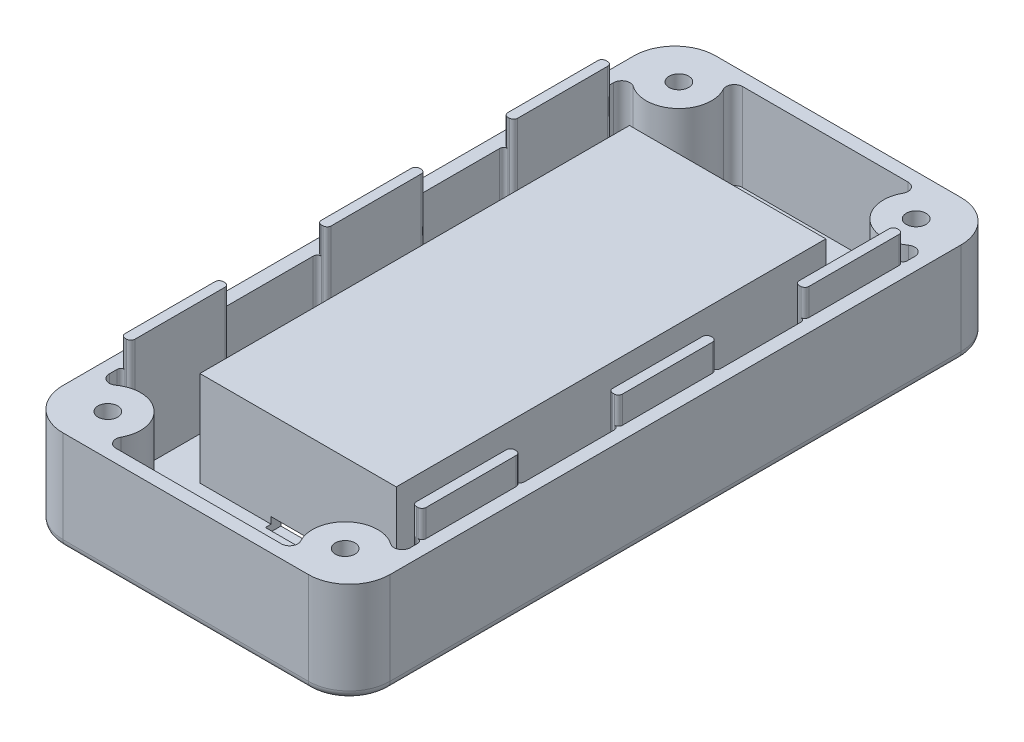
SolidWorks part; units mm, degrees
ref_plane "Front Plane" through (0, 0, 0) normal (0, 0, 1) x (1, 0, 0)
ref_plane "Top Plane" through (0, 0, 0) normal (0, 1, 0) x (1, 0, 0)
ref_plane "Right Plane" through (0, 0, 0) normal (1, 0, 0) x (0, 0, -1)
sketch "Base Sketch" plane through (0, 0, 0) normal (0, 1, 0) x (1, 0, 0)
  line L1 (0, 0) -> (40, 0)
  line L2 (0, 0) -> (0, 79.79)
  line L3 (0, 79.79) -> (40, 79.79)
  line L4 (40, 0) -> (40, 79.79)
extrude "Base" add sketch "Base Sketch" along normal blind 12.3
fillet "Corner Rounds R5" radius 5 4 edges at (0, 6.15, -79.79) (40, 6.15, -79.79) (40, 6.15, 0) (0, 6.15, 0)
shell "Shell" thickness 1.6 removed face at (20, 12.3, -39.895)
sketch "Sketch2" plane through (0, 0, 0) normal (0, 1, 0) x (1, 0, 0)
  circle A0 centre (5.5, 5) radius 4
  circle A1 centre (34.5, 5) radius 4
  circle A2 centre (5.5, 74.79) radius 4
  circle A3 centre (34.5, 74.79) radius 4
extrude "Screw Bosses" add sketch "Sketch2" along normal blind 12.3
sketch "Sketch3" plane through (0, 0, 0) normal (0, 1, 0) x (1, 0, 0)
  line L1 (1.6, 10.5) -> (2.8, 10.5)
  line L2 (1.6, 10.5) -> (1.6, 22.5)
  line L3 (1.6, 22.5) -> (2.8, 22.5)
  line L4 (2.8, 10.5) -> (2.8, 22.5)
  line L6 (1.6, 34.5) -> (2.8, 34.5)
  line L7 (1.6, 34.5) -> (1.6, 46.5)
  line L8 (1.6, 46.5) -> (2.8, 46.5)
  line L9 (2.8, 34.5) -> (2.8, 46.5)
  line L11 (1.6, 57.29) -> (2.8, 57.29)
  line L12 (1.6, 57.29) -> (1.6, 69.29)
  line L13 (1.6, 69.29) -> (2.8, 69.29)
  line L14 (2.8, 57.29) -> (2.8, 69.29)
  line L16 (37.2, 10.5) -> (38.4, 10.5)
  line L17 (37.2, 10.5) -> (37.2, 22.5)
  line L18 (37.2, 22.5) -> (38.4, 22.5)
  line L19 (38.4, 10.5) -> (38.4, 22.5)
  line L21 (37.2, 34.5) -> (38.4, 34.5)
  line L22 (37.2, 34.5) -> (37.2, 46.5)
  line L23 (37.2, 46.5) -> (38.4, 46.5)
  line L24 (38.4, 34.5) -> (38.4, 46.5)
  line L26 (37.2, 57.29) -> (38.4, 57.29)
  line L27 (37.2, 57.29) -> (37.2, 69.29)
  line L28 (37.2, 69.29) -> (38.4, 69.29)
  line L29 (38.4, 57.29) -> (38.4, 69.29)
extrude "Alignment Tabs" add sketch "Sketch3" along normal blind 15.6
fillet "Bottom Edge Round R1" radius 1 8 edges at (1.4645, 0, -1.4645) (20, 0, 0) (38.5355, 0, -1.4645) (40, 0, -39.895) (38.5355, 0, -78.3255) (20, 0, -79.79) (1.4645, 0, -78.3255) (0, 0, -39.895)
sketch "Sketch4" plane through (0, 0, 0) normal (0, 1, 0) x (1, 0, 0)
  circle A0 centre (5.5, 5) radius 1.2
  circle A1 centre (34.5, 5) radius 1.2
  circle A2 centre (5.5, 74.79) radius 1.2
  circle A3 centre (34.5, 74.79) radius 1.2
extrude "M2 Clearance Holes" cut sketch "Sketch4" along normal through all
sketch "Sketch5" plane through (0, 0, 0) normal (0, 1, 0) x (1, 0, 0)
  circle A0 centre (5.5, 5) radius 2.2
  circle A1 centre (34.5, 5) radius 2.2
  circle A2 centre (5.5, 74.79) radius 2.2
  circle A3 centre (34.5, 74.79) radius 2.2
extrude "M2 Counterbores" cut sketch "Sketch5" along normal blind 8.3
fillet "Lug Junction Fillets R1" radius 1 8 edges at (32.3929, 6.95, -78.19) (38.4, 6.95, -73.9012) (7.6071, 6.95, -78.19) (1.6, 6.95, -73.9012) (32.3929, 6.95, -1.6) (38.4, 6.95, -5.8888) (7.6071, 6.95, -1.6) (1.6, 6.95, -5.8888)
chamfer "Chamfer2" distance 1 angle 45 4 edges at (5.5, 8.3, -2.8) (34.5, 8.3, -2.8) (34.5, 8.3, -72.59) (5.5, 8.3, -72.59)
fillet "Fillet2" radius 0.5 24 edges at (37.2, 8.6, -69.29) (38.4, 6.95, -69.29) (37.2, 8.6, -57.29) (37.2, 8.6, -46.5) (37.2, 8.6, -34.5) (37.2, 8.6, -22.5) (37.2, 8.6, -10.5) (2.8, 8.6, -69.29) (2.8, 8.6, -57.29) (2.8, 8.6, -46.5) (2.8, 8.6, -34.5) (2.8, 8.6, -22.5) (2.8, 8.6, -10.5) (38.4, 6.95, -57.29) (38.4, 6.95, -46.5) (38.4, 6.95, -34.5) (38.4, 6.95, -22.5) (38.4, 6.95, -10.5) (1.6, 6.95, -69.29) (1.6, 6.95, -57.29) (1.6, 6.95, -46.5) (1.6, 6.95, -34.5) (1.6, 6.95, -22.5) (1.6, 6.95, -10.5)
fillet "Tab Top Corner Fillets R0.5" radius 0.5 12 edges at (38.4, 13.95, -57.29) (38.4, 13.95, -69.29) (38.4, 13.95, -34.5) (38.4, 13.95, -46.5) (38.4, 13.95, -10.5) (38.4, 13.95, -22.5) (1.6, 13.95, -57.29) (1.6, 13.95, -69.29) (1.6, 13.95, -34.5) (1.6, 13.95, -46.5) (1.6, 13.95, -22.5) (1.6, 13.95, -10.5)
sketch "Battery Compartment Block Sketch" plane through (0, 0, 0) normal (0, 1, 0) x (1, 0, 0)
  line L0 (8, 13.75) -> (32, 13.75)
  line L1 (32, 13.75) -> (32, 66.25)
  line L2 (32, 66.25) -> (8, 66.25)
  line L3 (8, 66.25) -> (8, 13.75)
extrude "Battery Compartment Block" add sketch "Battery Compartment Block Sketch" along normal blind 13.2
sketch "Battery Door Opening Sketch" plane through (0, 0, 0) normal (0, 1, 0) x (1, 0, 0)
  line L0 (9.2, 14.95) -> (30.8, 14.95)
  line L1 (30.8, 14.95) -> (30.8, 65.05)
  line L2 (30.8, 65.05) -> (9.2, 65.05)
  line L3 (9.2, 65.05) -> (9.2, 14.95)
extrude "Battery Door Opening" cut sketch "Battery Door Opening Sketch" along normal blind 1.6
sketch "Cell Channels 10.2 x 46.7 Sketch" plane through (0, 0, 0) normal (0, 1, 0) x (1, 0, 0)
  line L0 (9.2, 16.65) -> (19.4, 16.65)
  line L1 (19.4, 16.65) -> (19.4, 63.35)
  line L2 (19.4, 63.35) -> (9.2, 63.35)
  line L3 (9.2, 63.35) -> (9.2, 16.65)
  line L4 (20.6, 16.65) -> (30.8, 16.65)
  line L5 (30.8, 16.65) -> (30.8, 63.35)
  line L6 (30.8, 63.35) -> (20.6, 63.35)
  line L7 (20.6, 63.35) -> (20.6, 16.65)
extrude "Cell Channels 10.2 x 46.7" cut sketch "Cell Channels 10.2 x 46.7 Sketch" along normal blind 12
sketch "Divider Relief (divider 7 tall) Sketch" plane through (0, 0, 0) normal (0, 1, 0) x (1, 0, 0)
  line L0 (19.4, 16.65) -> (20.6, 16.65)
  line L1 (20.6, 16.65) -> (20.6, 63.35)
  line L2 (20.6, 63.35) -> (19.4, 63.35)
  line L3 (19.4, 63.35) -> (19.4, 16.65)
extrude "Divider Relief (divider 7 tall)" cut sketch "Divider Relief (divider 7 tall) Sketch" along normal blind 5
sketch "Clip Slots 0.7 Sketch" plane through (0, 0, 0) normal (0, 1, 0) x (1, 0, 0)
  line L0 (9.05, 14.95) -> (30.95, 14.95)
  line L1 (30.95, 14.95) -> (30.95, 15.65)
  line L2 (30.95, 15.65) -> (9.05, 15.65)
  line L3 (9.05, 15.65) -> (9.05, 14.95)
  line L4 (9.15, 64.35) -> (19.45, 64.35)
  line L5 (19.45, 64.35) -> (19.45, 65.05)
  line L6 (19.45, 65.05) -> (9.15, 65.05)
  line L7 (9.15, 65.05) -> (9.15, 64.35)
  line L8 (20.55, 64.35) -> (30.85, 64.35)
  line L9 (30.85, 64.35) -> (30.85, 65.05)
  line L10 (30.85, 65.05) -> (20.55, 65.05)
  line L11 (20.55, 65.05) -> (20.55, 64.35)
extrude "Clip Slots 0.7" cut sketch "Clip Slots 0.7 Sketch" along normal blind 12
ref_plane "Contact Opening Plane d15.65" through (0, 0, -15.65) normal (0, 0, 1) x (1, 0, 0)
sketch "Contact Openings 5mm (U, open to door) Sketch" plane through (0, 0, -15.65) normal (0, 0, 1) x (1, 0, 0)
  line L0 (11.8, 0) -> (11.8, 6.95)
  line L1 (16.8, 6.95) -> (16.8, 0)
  line L2 (16.8, 0) -> (11.8, 0)
  line L3 (23.2, 0) -> (23.2, 6.95)
  line L4 (28.2, 6.95) -> (28.2, 0)
  line L5 (28.2, 0) -> (23.2, 0)
  arc A0 (11.8, 6.95) -> (16.8, 6.95) centre (14.3, 6.95) cw
  arc A1 (23.2, 6.95) -> (28.2, 6.95) centre (25.7, 6.95) cw
extrude "Contact Openings 5mm (U, open to door)" cut sketch "Contact Openings 5mm (U, open to door) Sketch" against normal blind 48.7
ref_plane "Floor Inner Plane y1.6" through (0, 1.6, 0) normal (0, 1, 0) x (1, 0, 0)
sketch "Wire Notches 3x2 (far end wall) Sketch" plane through (0, 1.6, 0) normal (0, 1, 0) x (1, 0, 0)
  line L0 (12.8, 65.05) -> (15.8, 65.05)
  line L1 (15.8, 65.05) -> (15.8, 66.25)
  line L2 (15.8, 66.25) -> (12.8, 66.25)
  line L3 (12.8, 66.25) -> (12.8, 65.05)
  line L4 (24.2, 65.05) -> (27.2, 65.05)
  line L5 (27.2, 65.05) -> (27.2, 66.25)
  line L6 (27.2, 66.25) -> (24.2, 66.25)
  line L7 (24.2, 66.25) -> (24.2, 65.05)
extrude "Wire Notches 3x2 (far end wall)" cut sketch "Wire Notches 3x2 (far end wall) Sketch" along normal blind 2
ref_plane "Door Lip Plane y0.8" through (0, 0.8, 0) normal (0, 1, 0) x (1, 0, 0)
sketch "Latch Hook Pocket (near) Sketch" plane through (0, 0.8, 0) normal (0, 1, 0) x (1, 0, 0)
  line L0 (16.7, 13.05) -> (23.3, 13.05)
  line L1 (23.3, 13.05) -> (23.3, 14.95)
  line L2 (23.3, 14.95) -> (16.7, 14.95)
  line L3 (16.7, 14.95) -> (16.7, 13.05)
extrude "Latch Hook Pocket (near)" cut sketch "Latch Hook Pocket (near) Sketch" along normal blind 1.6
sketch "Latch Finger Relief (F1 middle) Sketch" plane through (0, 1.6, 0) normal (0, 1, 0) x (1, 0, 0)
  line L0 (16.8, 15.65) -> (23.2, 15.65)
  line L1 (23.2, 15.65) -> (23.2, 16.65)
  line L2 (23.2, 16.65) -> (16.8, 16.65)
  line L3 (16.8, 16.65) -> (16.8, 15.65)
extrude "Latch Finger Relief (F1 middle)" cut sketch "Latch Finger Relief (F1 middle) Sketch" along normal blind 1
sketch "Door Tongue Pockets (far) Sketch" plane through (0, 0.8, 0) normal (0, 1, 0) x (1, 0, 0)
  line L0 (9.85, 65.05) -> (12.65, 65.05)
  line L1 (12.65, 65.05) -> (12.65, 66.01)
  line L2 (12.65, 66.01) -> (9.85, 66.01)
  line L3 (9.85, 66.01) -> (9.85, 65.05)
  line L4 (15.85, 65.05) -> (24.15, 65.05)
  line L5 (24.15, 65.05) -> (24.15, 66.01)
  line L6 (24.15, 66.01) -> (15.85, 66.01)
  line L7 (15.85, 66.01) -> (15.85, 65.05)
  line L8 (27.35, 65.05) -> (30.15, 65.05)
  line L9 (30.15, 65.05) -> (30.15, 66.01)
  line L10 (30.15, 66.01) -> (27.35, 66.01)
  line L11 (27.35, 66.01) -> (27.35, 65.05)
extrude "Door Tongue Pockets (far)" cut sketch "Door Tongue Pockets (far) Sketch" along normal blind 0.9
